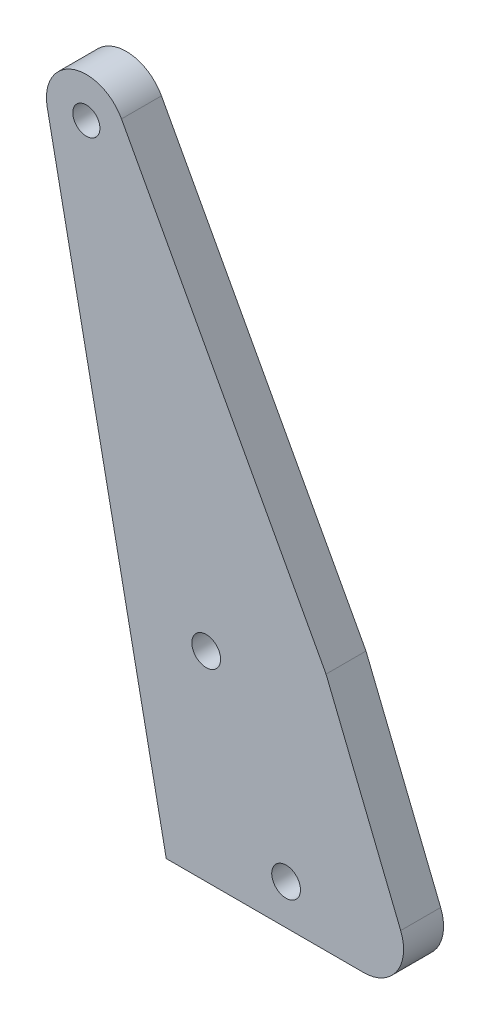
SolidWorks part; units mm, degrees
ref_plane "Front Plane" through (0, 0, 0) normal (0, 0, 1) x (1, 0, 0)
ref_plane "Top Plane" through (0, 0, 0) normal (0, 1, 0) x (1, 0, 0)
ref_plane "Right Plane" through (0, 0, 0) normal (1, 0, 0) x (0, 0, -1)
sketch "Sketch1" plane through (0, 0, 0) normal (0, 0, 1) x (1, 0, 0)
  line L1 (0, 0) -> (-25.4, 0)
  line L6 (-32.5135, 98.2688) -> (0, 38.1)
  line L7 (-44.3251, 93.9967) -> (-25.4, 0)
  line L9 (0, 38.1) -> (15.3934, 0)
  line L10 (15.3934, 0) -> (0, 0)
  line L11 (0, 38.1) -> (0, 0) construction
  line L12 (0, -22.9119) -> (0, 35.6119) construction
  arc A1 (-32.5135, 98.2688) -> (-44.3251, 93.9967) centre (-38.1, 95.25) ccw
  circle A2 centre (-6.35, 6.35) radius 2.286
  circle A3 centre (-19.05, 31.75) radius 2.286
  circle A4 centre (-38.1, 95.25) radius 2.159
  dimension "D3" = 95.25
  dimension "D5" = 12.7
  dimension "D7" = 4.572
  dimension "D4" = 6.35
  dimension ".17" = 4.318
  dimension "D6" = 38.1
  dimension "D1" = 25.4
  dimension "D2" = 38.1
  dimension "D8" = 31.75
  dimension "D9" = 19.05
  dimension "D11" = 6.35
  dimension "D12" = 22
extrude "Boss-Extrude1" add sketch "Sketch1" against normal blind 6.35
fillet "Fillet1" radius 6.35 1 edges at (15.3934, 0, -3.175)
